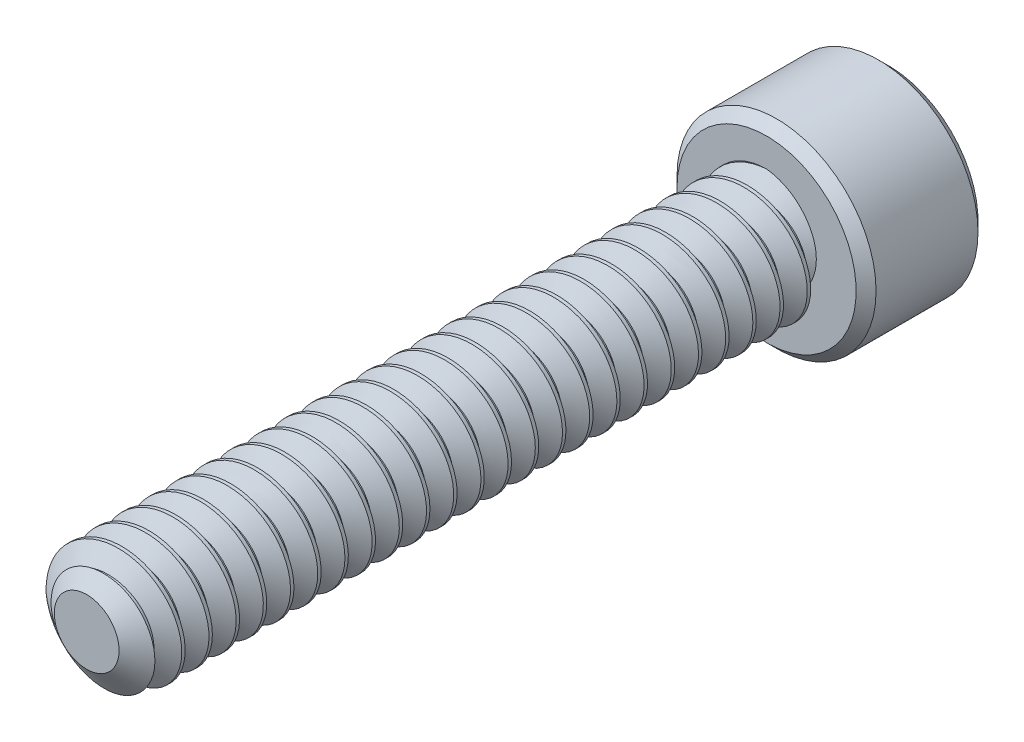
SolidWorks part; units mm, degrees
other "DetailItem1"
ref_plane "Front Plane" through (0, 0, 0) normal (0, 0, 1) x (1, 0, 0)
ref_plane "Top Plane" through (0, 0, 0) normal (0, 1, 0) x (1, 0, 0)
ref_plane "Right Plane" through (0, 0, 0) normal (1, 0, 0) x (0, 0, -1)
sketch "Sketch1" plane through (0, 0, 0) normal (0, 0, 1) x (1, 0, 0)
  circle A0 centre (0, 0) radius 1.4224
  dimension "OD" = 2.8448
extrude "Extrude1" add sketch "Sketch1" against normal blind 15.875
sketch "Sketch2" plane through (0, 0, 0) normal (0, 0, 1) x (1, 0, 0)
  circle A0 centre (0, 0) radius 1.4224 construction
  circle A1 centre (0, 0) radius 1.4224
curve "Helix/Spiral1" pitch 0.635 height 16.51 radius 1.4224 centre (0, 0, 0) axis (0, 0, -1) start towards (0, 1, 0) parameters "pitch"=0.635
sketch "Sketch3" plane through (0, 0, 0) normal (1, 0, 0) x (0, 0, -1)
  line L0 (-0.5556, 1.4224) -> (-0.3175, 1.01)
  line L1 (-0.3175, 1.01) -> (-0.2381, 1.01)
  line L2 (-0.2381, 1.01) -> (0, 1.4224)
  line L3 (-0.5556, 1.4224) -> (0, 1.4224)
  line L4 (-0.2778, 1.4224) -> (-0.2778, 1.01) construction
  line L5 (-0.4366, 1.2162) -> (-0.1191, 1.2162) construction
  line L6 (0, 1.4224) -> (0, -1.4224) construction
  dimension "D1" = 0.0794
  dimension "D2" = 0.3175
  dimension "D3" = 60
sweep "Cut-Sweep1" cut profiles "Sketch3" path "Helix/Spiral1"
sketch "Sketch4" plane through (0, 0, 0) normal (1, 0, 0) x (0, 0, -1)
  line L0 (0.4666, 1.4224) -> (0, 0.756)
  line L1 (0, 0.756) -> (0, 1.4224)
  line L2 (0.4666, 1.4224) -> (0, 1.4224)
  line L3 (-0.5556, 1.4224) -> (0, 1.4224) construction
  line L4 (0, 0) -> (7.0209, 0) construction
  dimension "D1" = 55
  dimension "D2" = 0.254
revolve "Cut-Revolve1" cut sketch "Sketch4" angle 360 about L4
sketch "Sketch6" plane through (0, 0, -15.875) normal (0, 0, -1) x (-1, 0, 0)
  circle A0 centre (0, 0) radius 2.3241
  dimension "head dia" = 4.6482
extrude "Extrude2" add sketch "Sketch6" along normal blind 2.8448
sketch "Sketch7" plane through (0, 0, -18.7198) normal (0, 0, -1) x (-1, 0, 0)
  line L1 (0, 1.3748) -> (-1.1906, 0.6874)
  line L2 (-1.1906, 0.6874) -> (-1.1906, -0.6874)
  line L3 (-1.1906, -0.6874) -> (0, -1.3748)
  line L4 (0, -1.3748) -> (1.1906, -0.6874)
  line L5 (1.1906, -0.6874) -> (1.1906, 0.6874)
  line L6 (1.1906, 0.6874) -> (0, 1.3748)
  circle A0 centre (0, 0) radius 1.1906 construction
  dimension "hex dia" = 2.3813
extrude "Cut-Extrude1" cut sketch "Sketch7" against normal blind 1.7859
sketch "Sketch8" plane through (0, 0, -18.7198) normal (0, 0, -1) x (-1, 0, 0)
  circle A0 centre (0, 0) radius 1.3748
extrude "Cut-Extrude2" cut sketch "Sketch8" against normal through all draft 45
chamfer "Chamfer1" distance 0.2324 angle 45 2 edges at (-2.3241, 0, -18.7198) (-2.3241, 0, -15.875)
sketch "Sketch10" plane through (0, 0, -15.875) normal (0, 0, 1) x (1, 0, 0)
  circle A1 centre (0, 0) radius 1.4224
  circle A2 centre (0, 0) radius 1.4224
  dimension "D1" = 0
ref_plane "Plane1" through (0, 0, -38.1) normal (0, 0, 1) x (1, 0, 0)
extrude "partial thread" [suppressed] add sketch "Sketch10" along normal up to surface (12.7 mm away) separate body
chamfer "Chamfer2" [suppressed] distance 0.0569 angle 45
combine bodies "Combine1" [suppressed] operation type add bodies to combine 107 108
sketch "Sketch9" plane through (0, 0, 0) normal (1, 0, 0) x (0, 0, -1)
  line L0 (0, 1.4224) -> (0, -1.4224) construction
  line L1 (1.5875, 1.4224) -> (1.5875, -1.4224) construction
  dimension "D1" = 1.5875
  dimension "D4" = 0.635
  dimension "D5" = 0.3302
equation "\"D3@Helix/Spiral1\" = \"screw length@Extrude1\"+\"pitch@Helix/Spiral1\""
equation "\"D1@Sketch3\" = \"pitch@Helix/Spiral1\"*.125"
equation "\"D2@Sketch3\" = \"pitch@Helix/Spiral1\"*.5"
equation "\"D1@Cut-Extrude1\" = \"hex dia@Sketch7\"*.75"
equation "\"D1@Chamfer1\" = \"head dia@Sketch6\"*.05"
equation "\"D1@Sketch9\" = \"pitch@Helix/Spiral1\"*2.5"
equation "\"D1@Chamfer2\"=\"OD@Sketch1\"*.02"
